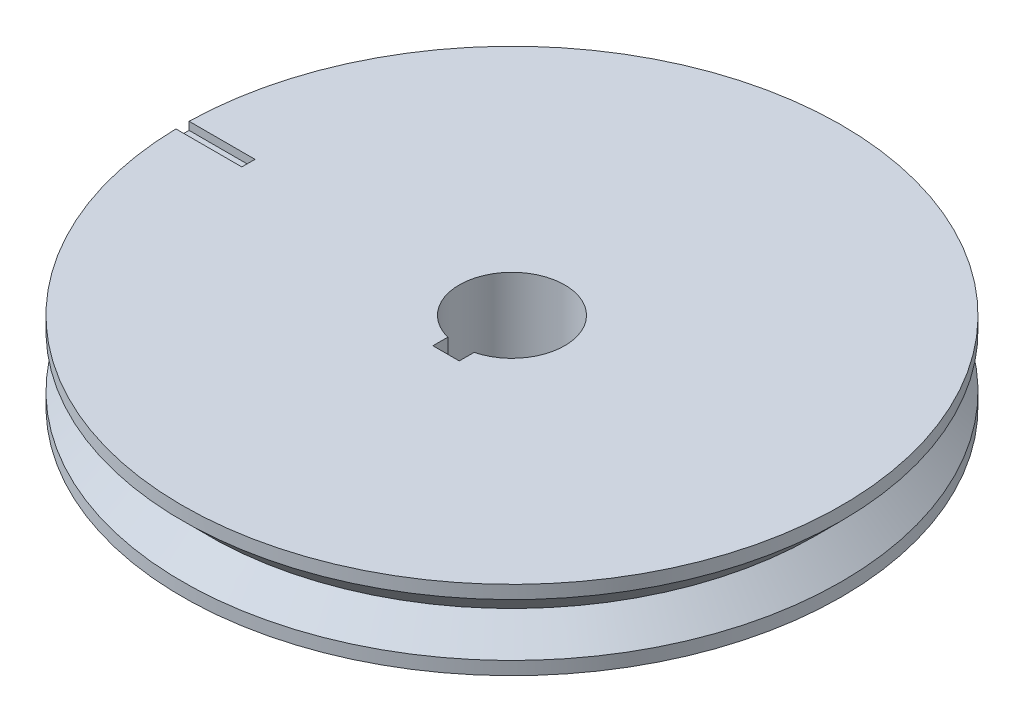
SolidWorks part; units mm, degrees
ref_plane "Front" through (0, 0, 0) normal (0, 0, 1) x (1, 0, 0)
ref_plane "Top" through (0, 0, 0) normal (0, 1, 0) x (1, 0, 0)
ref_plane "Right" through (0, 0, 0) normal (1, 0, 0) x (0, 0, -1)
sketch "Sketch1" plane through (0, 0, 0) normal (0, 0, 1) x (1, 0, 0)
  line L0 (0, 0) -> (115, 0) construction
  line L1 (0, 15) -> (125, 15)
  line L2 (0, 15) -> (0, -15)
  line L3 (0, -15) -> (125, -15)
  line L4 (125, 15) -> (125, 10)
  line L5 (115, 0) -> (125, 10)
  line L6 (115, 0) -> (125, -10)
  line L7 (125, -10) -> (125, -15)
  line L8 (0, -15) -> (0, -47.2315) construction
  dimension "D2" = 30
  dimension "D3" = 20
  dimension "OD" = 250
revolve "Revolve1" add sketch "Sketch1" angle 360 about L8
sketch "Sketch2" plane through (0, 15, 0) normal (0, 1, 0) x (-1, 0, 0)
  line L2 (-5, 19.3649) -> (-5, 25)
  line L3 (-5, 25) -> (5, 25)
  line L4 (5, 19.3649) -> (5, 25)
  arc A0 (-5, 19.3649) -> (5, 19.3649) centre (0, 0) ccw
  point P1 (0, 25)
  dimension "D1" = 40
  dimension "D2" = 25
  dimension "D3" = 10
extrude "Cut-Extrude1" cut sketch "Sketch2" against normal through all
sketch "Sketch3" plane through (0, 15, 0) normal (0, 1, 0) x (-1, 0, 0)
  line L0 (0, 0) -> (99.975, 0) construction
  line L1 (99.975, -2.5) -> (124.975, -2.5)
  line L2 (99.975, -2.5) -> (99.975, 2.5)
  line L3 (99.975, 2.5) -> (124.975, 2.5)
  circle A0 centre (0, 0) radius 125 construction
  arc A1 (124.975, -2.5) -> (124.975, 2.5) centre (0, 0) ccw
  dimension "D1" = 5
  dimension "D2" = 25
extrude "Cut-Extrude3" cut sketch "Sketch3" against normal blind 3
ref_axis "Axis1" through (0, 50, 0) along (0, -1, 0)
sketch "Sketch4" plane through (0, 15, 0) normal (0, 1, 0) x (-1, 0, 0)
  circle A0 centre (0, 110) radius 20
  dimension "D2" = 40
  dimension "D1" = 110
extrude "Extrude1" [suppressed] add sketch "Sketch4" along normal blind 50
